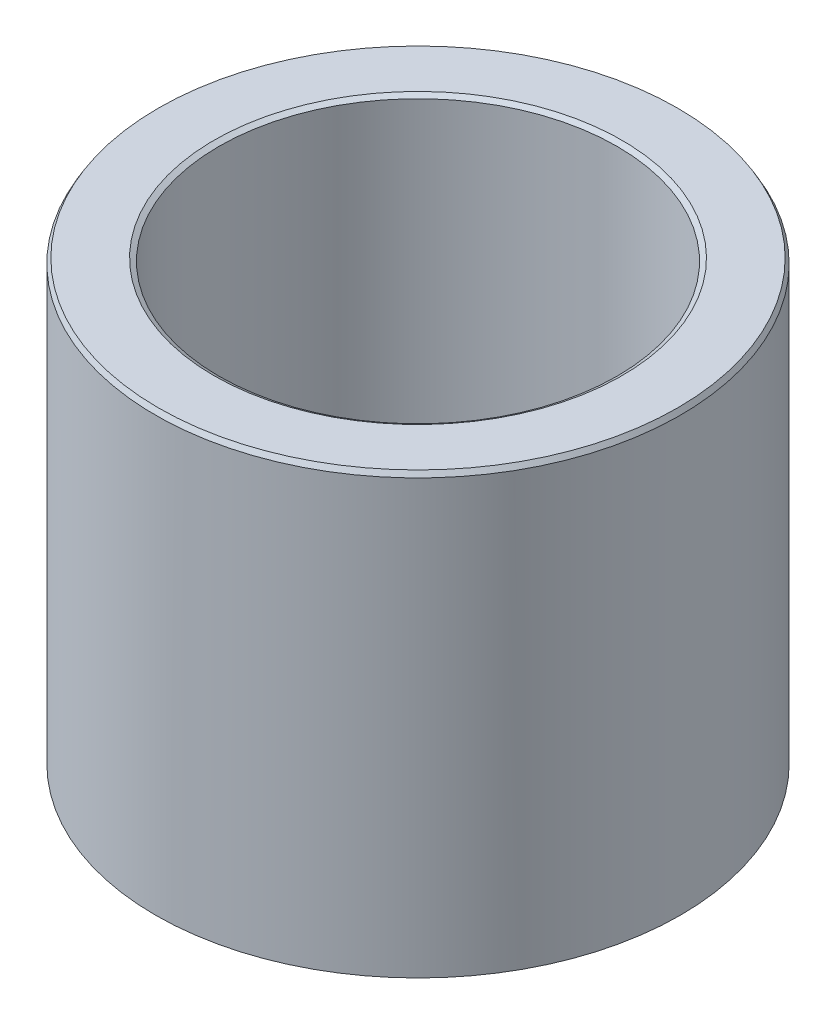
SolidWorks part; units mm, degrees
ref_plane "Front Plane" through (0, 0, 0) normal (0, 0, 1) x (1, 0, 0)
ref_plane "Top Plane" through (0, 0, 0) normal (0, 1, 0) x (1, 0, 0)
ref_plane "Right Plane" through (0, 0, 0) normal (1, 0, 0) x (0, 0, -1)
sketch "Sketch1" plane through (0, 0, 0) normal (0, 1, 0) x (1, 0, 0)
  circle A0 centre (0, 0) radius 17.5
  dimension "SLEEVE_OD" = 35
extrude "Boss-Extrude1" add sketch "Sketch1" along normal blind 29.3909
sketch "Sketch2" plane through (0, 0, 0) normal (0, 1, 0) x (1, 0, 0)
  circle A0 centre (0, 0) radius 13.2737
  dimension "BORE_D" = 26.5475
extrude "Cut-Extrude1" cut sketch "Sketch2" along normal through all
chamfer "Chamfer1" distance 0.3273 angle 30 4 edges at (0, 29.3909, 13.2737) (0, 0, 13.2737) (0, 0, 17.5) (0, 29.3909, 17.5) first distance on face at (0, 29.3909, 13.2737) first distance on face at (0, 0, 13.2737) first distance on face at (0, 29.3909, 17.5)
